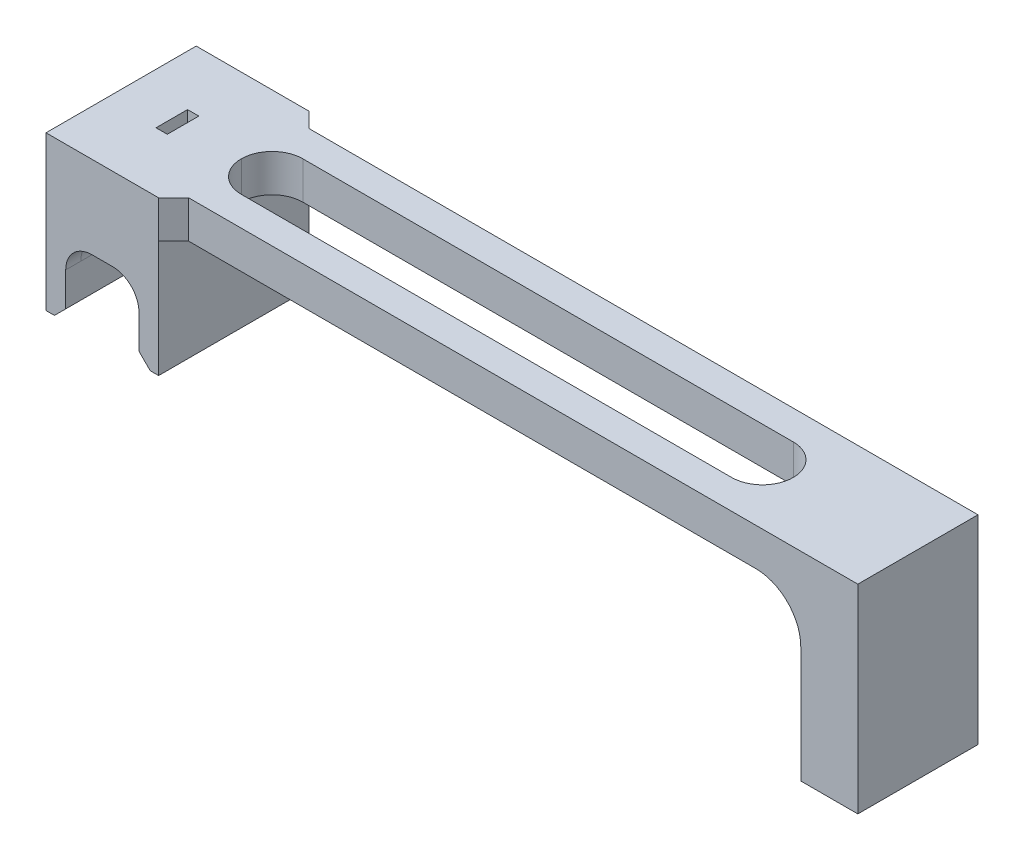
SolidWorks part; units mm, degrees
ref_plane "정면" through (0, 0, 0) normal (0, 0, 1) x (1, 0, 0)
ref_plane "윗면" through (0, 0, 0) normal (0, 1, 0) x (1, 0, 0)
ref_plane "우측면" through (0, 0, 0) normal (1, 0, 0) x (0, 0, -1)
sketch "스케치1" plane through (0, 0, 0) normal (0, 0, 1) x (1, 0, 0)
  line L0 (-96, 0) -> (0, 0)
  line L1 (0, 0) -> (0, -21.5)
  line L2 (0, -21.5) -> (7.6, -21.5)
  line L3 (7.6, -21.5) -> (7.6, 5)
  line L4 (7.6, 5) -> (-96, 5)
  line L5 (-96, 5) -> (-96, 0)
  dimension "D1" = 5
  dimension "D2" = 96
  dimension "D3" = 7.6
  dimension "D4" = 21.5
extrude "보스-돌출1" add sketch "스케치1" along normal blind 16
sketch "스케치4" plane through (0, 0, 0) normal (0, -1, 0) x (1, 0, 0)
  line L0 (-96, 8) -> (-7.1358, 8) construction
  line L1 (-96, 16) -> (-96, 0) construction
  line L2 (0, 16) -> (0, 0) construction
  line L3 (-91.75, 5.9) -> (-90.25, 5.9)
  line L4 (-91.75, 5.9) -> (-91.75, 10.1)
  line L5 (-91.75, 10.1) -> (-90.25, 10.1)
  line L6 (-90.25, 5.9) -> (-90.25, 10.1)
  line L7 (-91.75, 5.9) -> (-90.25, 10.1) construction
  line L8 (-91.75, 10.1) -> (-90.25, 5.9) construction
  line L9 (-9, 3.9) -> (-82.5, 3.9)
  line L10 (-9, 3.9) -> (-9, 12.1)
  line L11 (-9, 12.1) -> (-82.5, 12.1)
  line L12 (-82.5, 3.9) -> (-82.5, 12.1)
  line L13 (-9, 3.9) -> (-82.5, 12.1) construction
  line L14 (-9, 12.1) -> (-82.5, 3.9) construction
  point P4 (-91, 8)
  point P9 (-45.75, 8)
  dimension "D1" = 1.5
  dimension "D2" = 4.25
  dimension "D3" = 7.75
  dimension "D4" = 9
  dimension "D5" = 8.2
  dimension "D6" = 4.2
extrude "컷-돌출1" cut sketch "스케치4" against normal blind 10
fillet "필렛1" radius 4.1 4 edges at (-82.5, 2.5, 3.9) (-82.5, 2.5, 12.1) (-9, 2.5, 3.9) (-9, 2.5, 12.1)
sketch "스케치6" plane through (0, 5, 0) normal (0, 1, 0) x (1, 0, 0)
  line L0 (7.6, -16) -> (-96, -16) construction
  line L1 (-96, 0) -> (-86, 0)
  line L2 (-96, 0) -> (-96, -16)
  line L3 (-96, -16) -> (-86, -16)
  line L4 (-86, 0) -> (-86, -16)
  line L6 (-90.25, -5.9) -> (-90.25, -10.1) construction
  line M5 (-91.75, -5.9) -> (-90.25, -5.9)
  line M6 (-90.25, -5.9) -> (-90.25, -10.1)
  line M7 (-90.25, -10.1) -> (-91.75, -10.1)
  line M8 (-91.75, -10.1) -> (-91.75, -5.9)
  line M15 (7.6, 0) -> (-96, 0)
  line M16 (-96, 0) -> (-96, -16)
  line M17 (-96, -16) -> (7.6, -16)
  dimension "D1" = 4.25
extrude "보스-돌출4" add sketch "스케치6" against normal blind 11 contours L4 M15 M16 M17 M8 M5 M6 M7 region at (-91, 5, 0.1887)
sketch "스케치10" plane through (0, -6, 0) normal (0, -1, 0) x (1, 0, 0)
  line L0 (-91, 10.1) -> (-91, 5.9) construction
  line L1 (-90.25, 10.1) -> (-91.75, 10.1) construction
  line L2 (-91.75, 5.9) -> (-90.25, 5.9) construction
  line L3 (-91.75, 8) -> (-90.25, 8) construction
  line L4 (-91.75, 10.1) -> (-91.75, 5.9) construction
  line L5 (-90.25, 5.9) -> (-90.25, 10.1) construction
  line L7 (-95.875, 0) -> (-86.125, 0)
  line L8 (-95.875, 0) -> (-95.875, 16)
  line L9 (-95.875, 16) -> (-86.125, 16)
  line L10 (-86.125, 0) -> (-86.125, 16)
  line L11 (-95.875, 0) -> (-86.125, 16) construction
  line L12 (-95.875, 16) -> (-86.125, 0) construction
  line L13 (-98.5, 0) -> (-83.5, 0)
  line L14 (-98.5, 0) -> (-98.5, 16)
  line L15 (-98.5, 16) -> (-83.5, 16)
  line L16 (-83.5, 0) -> (-83.5, 16)
  line L17 (-98.5, 0) -> (-83.5, 16) construction
  line L18 (-98.5, 16) -> (-83.5, 0) construction
  point P12 (-91, 8)
  point P17 (-91, 8)
  line M6 (-86, 0) -> (-86, 16)
  line M7 (-86, 16) -> (-96, 16)
  line M8 (-96, 16) -> (-96, 0)
  line M9 (-96, 0) -> (-86, 0)
  dimension "D1" = 9.75
  dimension "D2" = 15
extrude "보스-돌출6" add sketch "스케치10" along normal blind 13 and the other way up to vertex (11 mm away) contours L8 M9 M7 M8 | L15 L14 L13 M8 | L10 M9 M6 M7 | L13 L16 L15 M6 region at (-95.9375, -6, 8) region at (-86.0625, -6, 8) region at (-97.25, -6, 8) region at (-84.75, -6, 8) other way up to point (7.6, 5, 16)
fillet "필렛2" radius 3.5 2 edges at (-86.125, -6, 8) (-95.875, -6, 8)
fillet "필렛3" radius 6 1 edges at (0, 0, 8)
sketch "스케치11" plane through (0, 0, 16) normal (0, 0, 1) x (1, 0, 0)
  line L0 (-98.5, 5) -> (-98.5, -19)
  line L1 (-98.5, -19) -> (-95.875, -19)
  line L2 (-92.375, -6) -> (-83.5, -6) construction
  line L3 (-83.5, -19) -> (-83.5, 0) construction
  line L4 (-83.5, -6) -> (-98.5, -6) construction
  line L5 (-95.875, -19) -> (-95.875, -6)
  line L6 (-86.125, -19) -> (-86.125, -6)
  line L7 (-86.125, -6) -> (-95.875, -6)
  line L8 (-86.125, -19) -> (-83.5, -19)
  line L9 (-83.5, -19) -> (-83.5, 5)
  line L10 (7.6, 5) -> (-98.5, 5) construction
  line L11 (-83.5, 5) -> (-98.5, 5)
extrude "보스-돌출7" add sketch "스케치11" along normal blind 2
sketch "스케치12" plane through (0, 0, 0) normal (0, 0, -1) x (-1, 0, 0)
  line L0 (89.625, -6) -> (98.5, -6) construction
  line L1 (98.5, 5) -> (98.5, -19) construction
  line L2 (98.5, -6) -> (83.5, -6) construction
  line L3 (83.5, -19) -> (83.5, 0) construction
  line L4 (83.5, 5) -> (83.5, -19)
  line L5 (-7.6, 5) -> (98.5, 5) construction
  line L6 (83.5, -19) -> (86.125, -19)
  line L7 (86.125, -19) -> (86.125, -6)
  line L8 (83.5, 5) -> (98.5, 5)
  line L9 (98.5, 5) -> (98.5, -19)
  line L10 (98.5, -19) -> (95.875, -19)
  line L11 (95.875, -19) -> (95.875, -6)
  line L12 (95.875, -6) -> (86.125, -6)
extrude "보스-돌출8" add sketch "스케치12" along normal blind 2
fillet "필렛4" radius 3.5 4 edges at (-95.875, -6, -1) (-86.125, -6, -1) (-86.125, -6, 17) (-95.875, -6, 17)
sketch "스케치13" plane through (-98.5, 0, 0) normal (-1, 0, 0) x (0, 0, 1)
  line L0 (18, 5) -> (18, -19) construction
  line L1 (-2, -19) -> (18, -19)
  line L2 (-2, -19) -> (-2, -15.5)
  line L3 (-2, -15.5) -> (18, -15.5)
  line L4 (18, -19) -> (18, -15.5)
  dimension "D1" = 3.5
extrude "컷-돌출2" cut sketch "스케치13" against normal up to vertex (15 mm away) up to point (-83.5, -19, -2)
chamfer "모따기1" distance 2 2 edges at (-83.5, 2.5, 16) (-83.5, 2.5, 0)
chamfer "모따기2" distance 1.5 angle 45 2 edges at (-95.875, -15.5, 8) (-86.125, -15.5, 8)
